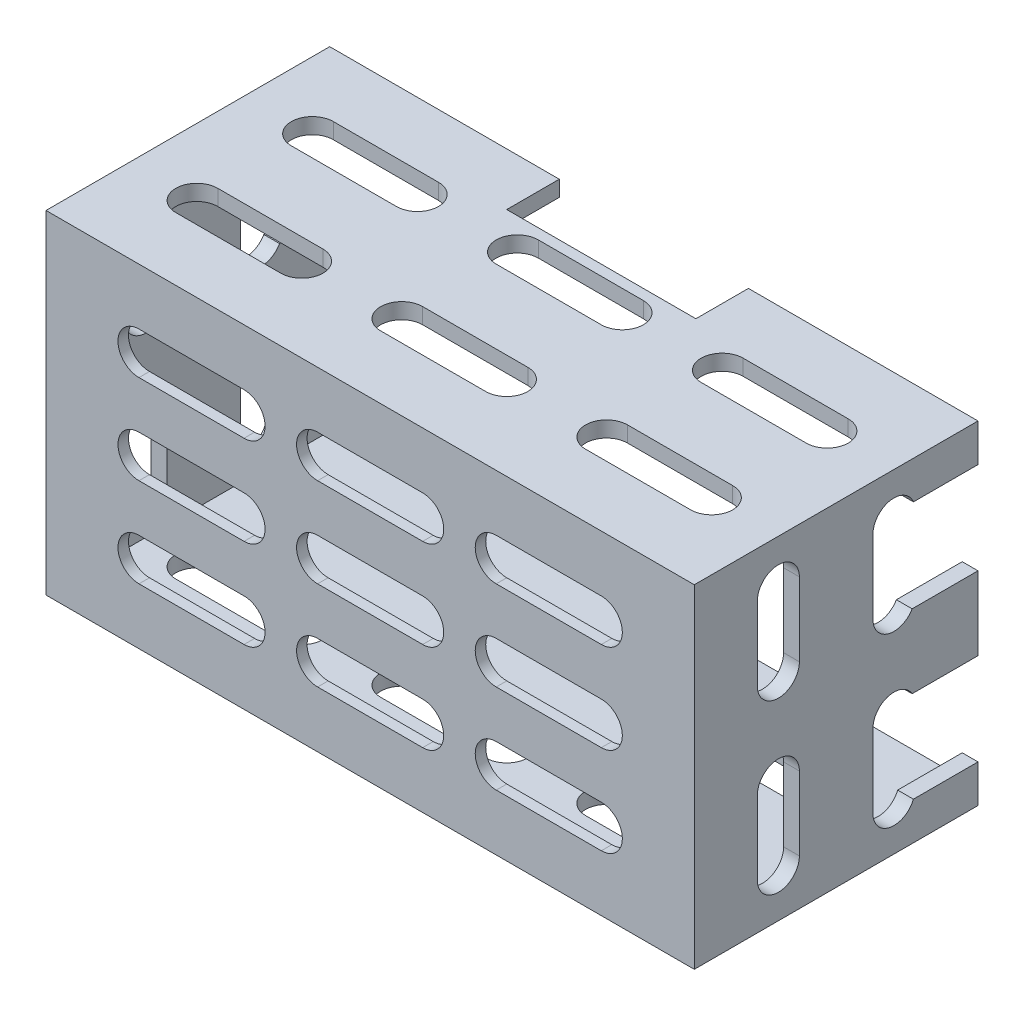
SolidWorks part; units mm, degrees
ref_plane "Front Plane" through (0, 0, 0) normal (0, 0, 1) x (1, 0, 0)
ref_plane "Top Plane" through (0, 0, 0) normal (0, 1, 0) x (1, 0, 0)
ref_plane "Right Plane" through (0, 0, 0) normal (1, 0, 0) x (0, 0, -1)
sketch "Sketch1" plane through (0, 0, 0) normal (0, 0, 1) x (1, 0, 0)
  line L4 (29.35, -14.35) -> (-29.35, -14.35)
  line L5 (29.25, -14.25) -> (-29.25, -14.25) construction
  line L6 (29.25, -14.25) -> (29.25, 14.25) construction
  line L7 (29.25, 14.25) -> (-29.25, 14.25) construction
  line L16 (-29.25, -14.25) -> (-29.25, 14.25) construction
  line L17 (-29.35, -14.35) -> (-29.35, 14.35)
  line L18 (29.35, 14.35) -> (-29.35, 14.35)
  line L19 (29.35, -14.35) -> (29.35, 14.35)
  line L20 (-30.85, -15.85) -> (-30.85, 15.85)
  line L21 (30.85, 15.85) -> (-30.85, 15.85)
  line L22 (30.85, -15.85) -> (30.85, 15.85)
  line L23 (30.85, -15.85) -> (-30.85, -15.85)
  dimension "D1" = 0.1
  dimension "D2" = 1.5
extrude "Boss-Extrude1" add sketch "Sketch1" along normal blind 21
sketch "Sketch2" plane through (0, 0, 21) normal (0, 0, 1) x (1, 0, 0)
  line L4 (-30.85, -15.85) -> (30.85, -15.85)
  line L5 (-30.85, -15.85) -> (30.85, -15.85)
  line L6 (-30.85, 15.85) -> (-30.85, -15.85)
  line L7 (30.85, 15.85) -> (-30.85, 15.85)
  line L10 (-30.85, 15.85) -> (-30.85, -15.85)
  line L11 (30.85, 15.85) -> (-30.85, 15.85)
  line L12 (30.85, -15.85) -> (30.85, 15.85)
  line L13 (30.85, -15.85) -> (30.85, 15.85)
  dimension "D1" = 0
extrude "Boss-Extrude2" add sketch "Sketch2" along normal blind 1
sketch "Sketch3" plane through (0, 0, 0) normal (0, 0, -1) x (-1, 0, 0)
  line L1 (29.35, -14.35) -> (-29.35, -14.35) construction
  line L4 (-30.85, -15.85) -> (30.85, -15.85)
  line L5 (30.85, 15.85) -> (-30.85, 15.85)
  line L6 (30.85, -15.85) -> (30.85, 15.85)
  line L7 (-30.85, -15.85) -> (30.85, -15.85)
  line L9 (30.85, 15.85) -> (9, 15.85)
  line L10 (30.85, -15.85) -> (30.85, 15.85)
  line L14 (29.35, 14.35) -> (29.35, -14.35) construction
  line L20 (-29.35, 14.35) -> (29.35, 14.35) construction
  line L21 (-29.35, -14.35) -> (-29.35, 14.35) construction
  line L22 (29.35, -14.35) -> (-29.35, -14.35)
  line L23 (29.35, 14.35) -> (29.35, -14.35)
  line L24 (-30.85, 15.85) -> (-30.85, -15.85)
  line L25 (-30.85, 15.85) -> (-30.85, -15.85)
  line L26 (-29.35, 14.35) -> (-9, 14.35)
  line L27 (-29.35, -14.35) -> (-29.35, 14.35)
  line L28 (-9, 14.35) -> (-9, 15.85)
  line L29 (9, 14.35) -> (9, 15.85)
  line L30 (-9, 15.85) -> (-30.85, 15.85)
  line L31 (9, 14.35) -> (29.35, 14.35)
  point P10 (9, 15.1)
  dimension "D2" = 18
  dimension "D1" = 0
extrude "Boss-Extrude3" add sketch "Sketch3" along normal up to surface (5 mm away)
sketch "Sketch8" plane through (0, 0, 21) normal (0, 0, -1) x (-1, 0, 0)
  line L0 (12, 6.5) -> (22, 6.5) construction
  line L1 (12, -2) -> (22, -2) construction
  line L2 (12, -10.5) -> (22, -10.5) construction
  line L3 (-5, -10.5) -> (5, -10.5) construction
  line L4 (-22, -10.5) -> (-12, -10.5) construction
  line L5 (-22, -2) -> (-12, -2) construction
  line L6 (-5, 6.5) -> (5, 6.5) construction
  line L7 (-22, 6.5) -> (-12, 6.5) construction
  line L8 (12, 6.5) -> (22, 6.5)
  line L9 (12, -2) -> (22, -2)
  line L10 (12, -10.5) -> (22, -10.5)
  line L11 (-5, -10.5) -> (5, -10.5)
  line L12 (-22, -10.5) -> (-12, -10.5)
  line L13 (-22, -2) -> (-12, -2)
  line L14 (-5, 6.5) -> (5, 6.5)
  line L15 (-22, 6.5) -> (-12, 6.5)
  line L16 (22, -6.5) -> (12, -6.5) construction
  line L17 (5, -6.5) -> (-5, -6.5) construction
  line L18 (-12, -6.5) -> (-22, -6.5) construction
  line L19 (22, 2) -> (12, 2) construction
  line L20 (-5, -2) -> (5, -2) construction
  line L21 (5, 2) -> (-5, 2) construction
  line L22 (-12, 2) -> (-22, 2) construction
  line L23 (22, 10.5) -> (12, 10.5) construction
  line L24 (5, 10.5) -> (-5, 10.5) construction
  line L25 (-12, 10.5) -> (-22, 10.5) construction
  line L26 (22, -6.5) -> (12, -6.5)
  line L27 (5, -6.5) -> (-5, -6.5)
  line L28 (-12, -6.5) -> (-22, -6.5)
  line L29 (22, 2) -> (12, 2)
  line L30 (-5, -2) -> (5, -2)
  line L31 (5, 2) -> (-5, 2)
  line L32 (-12, 2) -> (-22, 2)
  line L33 (22, 10.5) -> (12, 10.5)
  line L34 (5, 10.5) -> (-5, 10.5)
  line L35 (-12, 10.5) -> (-22, 10.5)
  arc A0 (22, -10.5) -> (22, -6.5) centre (22, -8.5) ccw construction
  arc A1 (12, -6.5) -> (12, -10.5) centre (12, -8.5) ccw construction
  arc A2 (5, -10.5) -> (5, -6.5) centre (5, -8.5) ccw construction
  arc A3 (-5, -6.5) -> (-5, -10.5) centre (-5, -8.5) ccw construction
  arc A4 (-12, -10.5) -> (-12, -6.5) centre (-12, -8.5) ccw construction
  arc A5 (-22, -6.5) -> (-22, -10.5) centre (-22, -8.5) ccw construction
  arc A6 (22, -2) -> (22, 2) centre (22, 0) ccw construction
  arc A7 (12, 2) -> (12, -2) centre (12, 0) ccw construction
  arc A8 (-5, 2) -> (-5, -2) centre (-5, 0) ccw construction
  arc A9 (5, -2) -> (5, 2) centre (5, 0) ccw construction
  arc A10 (-12, -2) -> (-12, 2) centre (-12, 0) ccw construction
  arc A11 (-22, 2) -> (-22, -2) centre (-22, 0) ccw construction
  arc A12 (22, 6.5) -> (22, 10.5) centre (22, 8.5) ccw construction
  arc A13 (12, 10.5) -> (12, 6.5) centre (12, 8.5) ccw construction
  arc A14 (-5, 10.5) -> (-5, 6.5) centre (-5, 8.5) ccw construction
  arc A15 (-12, 6.5) -> (-12, 10.5) centre (-12, 8.5) ccw construction
  arc A16 (-22, 10.5) -> (-22, 6.5) centre (-22, 8.5) ccw construction
  arc A17 (22, -10.5) -> (22, -6.5) centre (22, -8.5) ccw
  arc A18 (12, -6.5) -> (12, -10.5) centre (12, -8.5) ccw
  arc A19 (5, -10.5) -> (5, -6.5) centre (5, -8.5) ccw
  arc A20 (-5, -6.5) -> (-5, -10.5) centre (-5, -8.5) ccw
  arc A21 (-12, -10.5) -> (-12, -6.5) centre (-12, -8.5) ccw
  arc A22 (-22, -6.5) -> (-22, -10.5) centre (-22, -8.5) ccw
  arc A23 (22, -2) -> (22, 2) centre (22, 0) ccw
  arc A24 (12, 2) -> (12, -2) centre (12, 0) ccw
  arc A25 (-5, 2) -> (-5, -2) centre (-5, 0) ccw
  arc A26 (5, -2) -> (5, 2) centre (5, 0) ccw
  arc A27 (-12, -2) -> (-12, 2) centre (-12, 0) ccw
  arc A28 (-22, 2) -> (-22, -2) centre (-22, 0) ccw
  arc A29 (22, 6.5) -> (22, 10.5) centre (22, 8.5) ccw
  arc A30 (12, 10.5) -> (12, 6.5) centre (12, 8.5) ccw
  arc A31 (-5, 10.5) -> (-5, 6.5) centre (-5, 8.5) ccw
  arc A32 (-12, 6.5) -> (-12, 10.5) centre (-12, 8.5) ccw
  arc A33 (-22, 10.5) -> (-22, 6.5) centre (-22, 8.5) ccw
  arc A34 (5, 6.5) -> (5, 10.5) centre (5, 8.5) ccw construction
  arc A35 (5, 6.5) -> (5, 10.5) centre (5, 8.5) ccw
extrude "Cut-Extrude4" cut sketch "Sketch8" against normal through all
sketch "Sketch5" plane through (-15, 15.85, 0) normal (0, -1, 0) x (1, 0, 0)
  line L0 (-9.5, 3) -> (0.5, 3) construction
  line L1 (-9.5, 5) -> (0.5, 5)
  line L2 (-9.5, 1) -> (0.5, 1)
  line L3 (-15.85, 8.5) -> (45.85, 8.5) construction
  line L4 (45.85, -5) -> (-15.85, -5) construction
  line L5 (-15.85, 22) -> (45.85, 22) construction
  line L6 (15, -5) -> (15, 22) construction
  line L7 (45.85, 14) -> (-15.85, 14) construction
  line L8 (-15.85, 22) -> (-15.85, -5) construction
  line L9 (-4.5, 22) -> (-4.5, -5) construction
  line L10 (45.85, 3) -> (-15.85, 3) construction
  line L11 (34.5, 22) -> (34.5, -5) construction
  line L13 (10, 1) -> (20, 1)
  line L14 (10, 5) -> (20, 5)
  line L15 (10, 3) -> (20, 3) construction
  line L16 (29.5, 1) -> (39.5, 1)
  line L17 (29.5, 5) -> (39.5, 5)
  line L18 (29.5, 3) -> (39.5, 3) construction
  line L19 (10, 12) -> (20, 12)
  line L20 (10, 16) -> (20, 16)
  line L21 (10, 14) -> (20, 14) construction
  line L22 (29.5, 12) -> (39.5, 12)
  line L23 (29.5, 16) -> (39.5, 16)
  line L24 (29.5, 14) -> (39.5, 14) construction
  line L25 (-9.5, 12) -> (0.5, 12)
  line L26 (-9.5, 16) -> (0.5, 16)
  line L27 (-9.5, 14) -> (0.5, 14) construction
  line L28 (45.85, 22) -> (45.85, -5) construction
  arc A0 (-9.5, 5) -> (-9.5, 1) centre (-9.5, 3) ccw
  arc A1 (0.5, 1) -> (0.5, 5) centre (0.5, 3) ccw
  arc A2 (10, 5) -> (10, 1) centre (10, 3) ccw
  arc A3 (20, 1) -> (20, 5) centre (20, 3) ccw
  arc A4 (29.5, 5) -> (29.5, 1) centre (29.5, 3) ccw
  arc A5 (39.5, 1) -> (39.5, 5) centre (39.5, 3) ccw
  arc A6 (10, 16) -> (10, 12) centre (10, 14) ccw
  arc A7 (20, 12) -> (20, 16) centre (20, 14) ccw
  arc A8 (29.5, 16) -> (29.5, 12) centre (29.5, 14) ccw
  arc A9 (39.5, 12) -> (39.5, 16) centre (39.5, 14) ccw
  arc A10 (-9.5, 16) -> (-9.5, 12) centre (-9.5, 14) ccw
  arc A11 (0.5, 12) -> (0.5, 16) centre (0.5, 14) ccw
  point P2 (-4.5, 3)
  point P15 (45.85, 8.5)
  point P29 (15, -5)
  point P31 (15, 3)
  point P38 (34.5, 3)
  point P45 (15, 14)
  point P52 (34.5, 14)
  point P59 (-4.5, 14)
  dimension "D1" = 10
  dimension "D2" = 4
  dimension "D3" = 39
  dimension "D4" = 11
  dimension "D5" = 3
  dimension "D6" = 2
extrude "Cut-Extrude2" cut sketch "Sketch5" along normal through all
sketch "Sketch7" plane through (30.85, -15, 0) normal (-1, 0, 0) x (0, 0, -1)
  line L0 (-14, -26.5) -> (-14, -19.5) construction
  line L1 (-16, -26.5) -> (-16, -19.5)
  line L2 (-12, -26.5) -> (-12, -19.5)
  line L3 (-22, -15) -> (5, -15) construction
  line L4 (-22, -30.85) -> (-22, 0.85) construction
  line L5 (5, 0.85) -> (5, -30.85) construction
  line L6 (-8.5, 0.85) -> (-8.5, -30.85) construction
  line L7 (-22, 0.85) -> (5, 0.85) construction
  line L8 (-22, -30.85) -> (5, -30.85) construction
  line L9 (-14, -30.85) -> (-14, 0.85) construction
  line L10 (-22, -7) -> (5, -7) construction
  line L11 (-22, -23) -> (5, -23) construction
  line L12 (-3, -30.85) -> (-3, 0.85) construction
  line L13 (-1, -26.5) -> (-1, -19.5)
  line L14 (-5, -26.5) -> (-5, -19.5)
  line L15 (-3, -26.5) -> (-3, -19.5) construction
  line L16 (-1, -10.5) -> (-1, -3.5)
  line L17 (-5, -10.5) -> (-5, -3.5)
  line L18 (-3, -10.5) -> (-3, -3.5) construction
  line L19 (-12, -10.5) -> (-12, -3.5)
  line L20 (-16, -10.5) -> (-16, -3.5)
  line L21 (-14, -10.5) -> (-14, -3.5) construction
  arc A0 (-16, -26.5) -> (-12, -26.5) centre (-14, -26.5) ccw
  arc A1 (-12, -19.5) -> (-16, -19.5) centre (-14, -19.5) ccw
  arc A2 (-5, -26.5) -> (-1, -26.5) centre (-3, -26.5) ccw
  arc A3 (-1, -19.5) -> (-5, -19.5) centre (-3, -19.5) ccw
  arc A4 (-5, -10.5) -> (-1, -10.5) centre (-3, -10.5) ccw
  arc A5 (-1, -3.5) -> (-5, -3.5) centre (-3, -3.5) ccw
  arc A6 (-16, -10.5) -> (-12, -10.5) centre (-14, -10.5) ccw
  arc A7 (-12, -3.5) -> (-16, -3.5) centre (-14, -3.5) ccw
  point P2 (-14, -23)
  point P16 (-22, -15)
  point P32 (-3, -23)
  point P39 (-3, -7)
  point P46 (-14, -7)
  dimension "D1" = 7
  dimension "D2" = 4
  dimension "D3" = 16
  dimension "D6" = 11
  dimension "D4" = 2
  dimension "D5" = 2
extrude "Cut-Extrude3" cut sketch "Sketch7" along normal through all
sketch "Sketch9" plane through (-30.85, 0, 0) normal (-1, 0, 0) x (0, 0, 1)
  line L0 (-5, 0) -> (22, 0) construction
  line L1 (-5, 3.5) -> (3, 3.5)
  line L2 (-5, 3.5) -> (-5, 12.25)
  line L3 (-5, 12.25) -> (3, 12.25)
  line L4 (3, 3.5) -> (3, 12.25)
  line L6 (-5, -15.85) -> (-5, 15.85) construction
  line L7 (22, 15.85) -> (22, -15.85) construction
  line L8 (3, -3.5) -> (3, -12.25)
  line L9 (-5, -12.25) -> (3, -12.25)
  line L10 (-5, -3.5) -> (-5, -12.25)
  line L11 (-5, -3.5) -> (3, -3.5)
  arc A0 (5, 11.5) -> (1, 11.5) centre (3, 11.5) ccw construction
  point P22 (3, 13.5)
extrude "Cut-Extrude5" cut sketch "Sketch9" against normal through all
